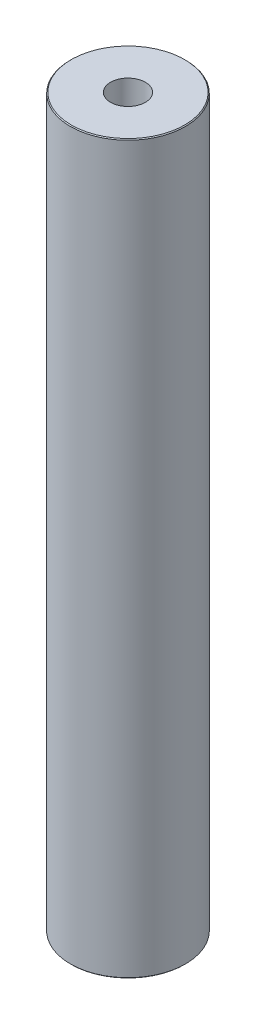
SolidWorks part; units mm, degrees
ref_plane "Front Plane" through (0, 0, 0) normal (0, 0, 1) x (1, 0, 0)
ref_plane "Top Plane" through (0, 0, 0) normal (0, 1, 0) x (1, 0, 0)
ref_plane "Right Plane" through (0, 0, 0) normal (1, 0, 0) x (0, 0, -1)
sketch "Sketch1" plane through (0, 0, 0) normal (0, 1, 0) x (1, 0, 0)
  circle A0 centre (0, 0) radius 47.5
  dimension "SHAFT_OD" = 95
extrude "Boss-Extrude1" add sketch "Sketch1" along normal blind 600
sketch "Sketch2" plane through (0, 0, 0) normal (0, 1, 0) x (1, 0, 0)
  circle A0 centre (0, 0) radius 14.3713
  dimension "BORE_D" = 28.7426
extrude "Cut-Extrude1" cut sketch "Sketch2" along normal through all
chamfer "Chamfer1" distance 0.7129 angle 45 2 edges at (0, 600, 47.5) (0, 0, 47.5)
